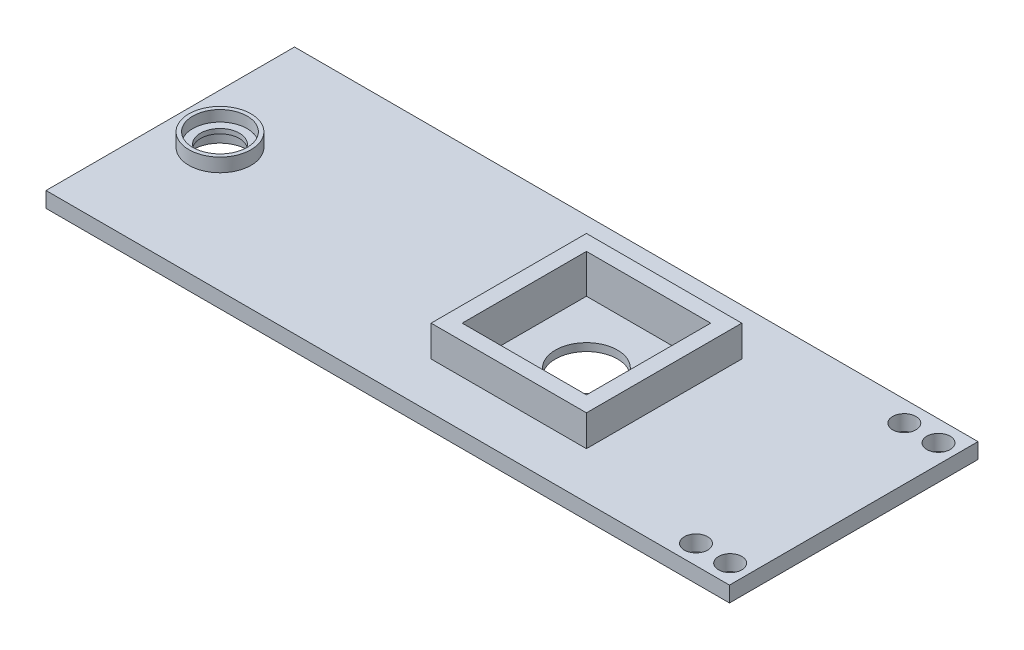
SolidWorks part; units mm, degrees
ref_plane "Front Plane" through (0, 0, 0) normal (0, 0, 1) x (1, 0, 0)
ref_plane "Top Plane" through (0, 0, 0) normal (0, 1, 0) x (1, 0, 0)
ref_plane "Right Plane" through (0, 0, 0) normal (1, 0, 0) x (0, 0, -1)
sketch "Sketch1" plane through (0, 0, 0) normal (0, 1, 0) x (1, 0, 0)
  line L1 (-304.8, -50.8) -> (-25.4, -50.8)
  line L2 (-304.8, -50.8) -> (-304.8, 50.8)
  line L3 (-304.8, 50.8) -> (-25.4, 50.8)
  line L4 (-25.4, -50.8) -> (-25.4, 50.8)
  point P0 (0, 0)
  dimension "D1" = 279.4
  dimension "D2" = 101.6
extrude "Boss-Extrude1" add sketch "Sketch1" along normal blind 6.35
sketch "Sketch2" plane through (0, 6.35, 0) normal (0, 1, 0) x (1, 0, 0)
  line L0 (-304.8, 50.8) -> (-304.8, -50.8) construction
  line L1 (-304.8, -50.8) -> (-25.4, -50.8) construction
  circle A0 centre (-284.48, 0) radius 12.7
  dimension "D1" = 25.4
  dimension "D2" = 20.32
  dimension "D3" = 50.8
extrude "Boss-Extrude3" add sketch "Sketch2" along normal blind 5.5562
sketch "Sketch9" plane through (0, 11.9062, 0) normal (0, 1, 0) x (1, 0, 0)
  circle A0 centre (-284.48, 0) radius 11.1125
extrude "Cut-Extrude4" cut sketch "Sketch9" against normal blind 4.445
sketch "Sketch10" plane through (0, 0, 0) normal (0, -1, 0) x (-1, 0, 0)
  circle A0 centre (284.48, 0) radius 11.1125
extrude "Cut-Extrude5" cut sketch "Sketch10" against normal blind 5.5562
sketch "Sketch11" plane through (0, 7.4613, 0) normal (0, 1, 0) x (1, 0, 0)
  circle A0 centre (-284.48, 0) radius 7.9375
extrude "Cut-Extrude6" cut sketch "Sketch11" against normal through all
sketch "Sketch12" plane through (0, 6.35, 0) normal (0, 1, 0) x (1, 0, 0)
  circle A0 centre (-134.6662, 0) radius 12.7
  dimension "D1" = 25.4
extrude "Cut-Extrude7" cut sketch "Sketch12" against normal through all
sketch "Sketch22" plane through (0, 6.35, 0) normal (0, 1, 0) x (1, 0, 0)
  line L1 (-102.9162, -31.75) -> (-166.4162, -31.75)
  line L2 (-102.9162, -31.75) -> (-102.9162, 31.75)
  line L3 (-102.9162, 31.75) -> (-166.4162, 31.75)
  line L4 (-166.4162, -31.75) -> (-166.4162, 31.75)
  line L5 (-102.9162, -31.75) -> (-166.4162, 31.75) construction
  line L6 (-102.9162, 31.75) -> (-166.4162, -31.75) construction
  circle A0 centre (-134.6662, 0) radius 12.7 construction
  point P0 (-134.6662, 0)
extrude "Boss-Extrude7" add sketch "Sketch22" along normal blind 12.7
sketch "Sketch25" plane through (0, 19.05, 0) normal (0, 1, 0) x (1, 0, 0)
  line L1 (-109.2662, -25.4) -> (-160.0662, -25.4)
  line L2 (-109.2662, -25.4) -> (-109.2662, 25.4)
  line L3 (-109.2662, 25.4) -> (-160.0662, 25.4)
  line L4 (-160.0662, -25.4) -> (-160.0662, 25.4)
  line L5 (-109.2662, -25.4) -> (-160.0662, 25.4) construction
  line L6 (-109.2662, 25.4) -> (-160.0662, -25.4) construction
  circle A0 centre (-134.6662, 0) radius 12.7 construction
  point P0 (-134.6662, 0)
  dimension "D1" = 50.8
  dimension "D2" = 50.8
extrude "Cut-Extrude11" cut sketch "Sketch25" against normal blind 15.875
sketch "Sketch32" plane through (0, 6.35, 0) normal (0, 1, 0) x (1, 0, 0)
  line L0 (-25.4, 50.8) -> (-304.8, 50.8) construction
  line L1 (-304.8, -50.8) -> (-25.4, -50.8) construction
  line L2 (-25.4, -50.8) -> (-25.4, 50.8) construction
  circle A0 centre (-33.02, -42.8938) radius 4.7625
  circle A1 centre (-46.99, -42.8938) radius 4.7625
  circle A2 centre (-33.02, 42.2729) radius 4.7625
  circle A3 centre (-46.99, 42.2729) radius 4.7625
  dimension "D1" = 9.525
  dimension "D2" = 9.525
  dimension "D3" = 9.525
  dimension "D4" = 9.525
  dimension "D5" = 8.5271
  dimension "D6" = 7.62
  dimension "D7" = 8.5271
  dimension "D8" = 21.59
  dimension "D9" = 7.9062
  dimension "D10" = 7.62
  dimension "D11" = 7.9062
  dimension "D12" = 21.59
extrude "Cut-Extrude12" cut sketch "Sketch32" against normal blind 6.35
